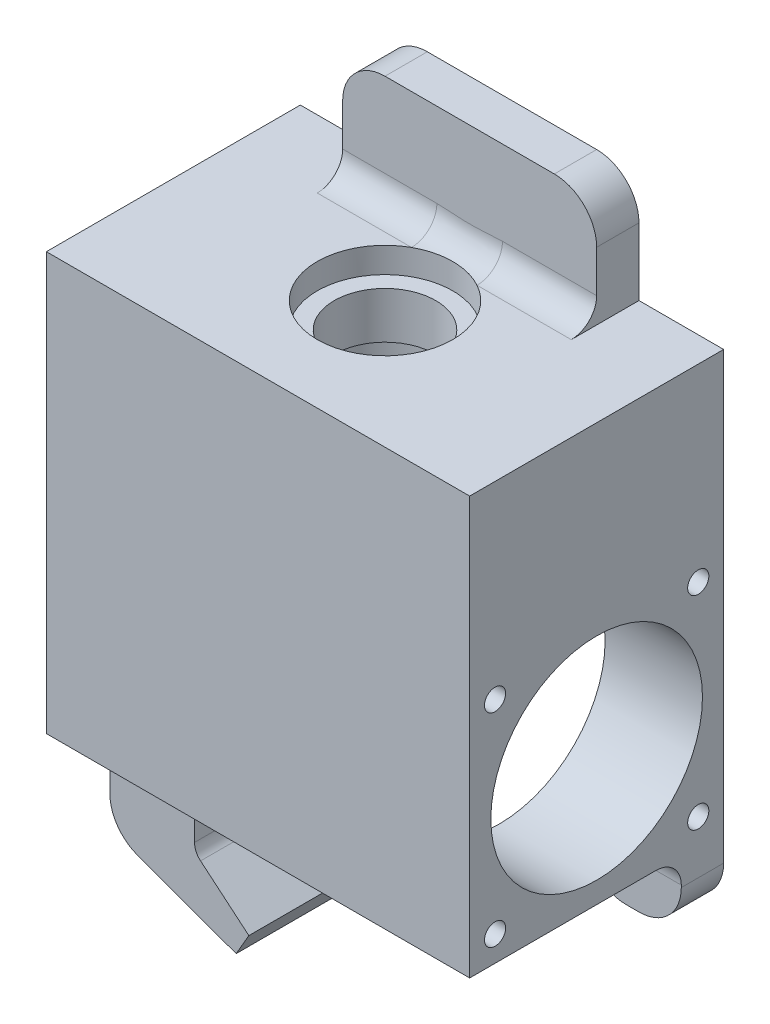
SolidWorks part; units mm, degrees
ref_plane "Спереди" through (0, 0, 0) normal (0, 0, 1) x (1, 0, 0)
ref_plane "Сверху" through (0, 0, 0) normal (0, 1, 0) x (1, 0, 0)
ref_plane "Справа" through (0, 0, 0) normal (1, 0, 0) x (0, 0, -1)
sketch "Эскиз1" plane through (0, 0, 0) normal (0, 0, 1) x (1, 0, 0)
  line L1 (25, -35.25) -> (-25, -35.25)
  line L2 (25, -35.25) -> (25, 35.25)
  line L3 (25, 35.25) -> (-25, 35.25)
  line L4 (-25, -35.25) -> (-25, 35.25)
  line L5 (25, -35.25) -> (-25, 35.25) construction
  line L6 (25, 35.25) -> (-25, -35.25) construction
  point P0 (0, 0)
  dimension "D1" = 50
  dimension "D2" = 70.5
extrude "Бобышка-Вытянуть1" add sketch "Эскиз1" along normal blind 30
sketch "Эскиз2" plane through (0, -35.25, 0) normal (0, -1, 0) x (1, 0, 0)
  line L0 (-25, 0) -> (25, 0) construction
  line L1 (-13.5, 15) -> (-13.5, 0)
  line L2 (-13.5, 0) -> (13.5, 0)
  line L3 (13.5, 0) -> (13.5, 15)
  arc A0 (13.5, 15) -> (-13.5, 15) centre (0, 15) ccw
  dimension "D1" = 27
  dimension "D2" = 15
extrude "Вырез-Вытянуть1" cut sketch "Эскиз2" against normal blind 46.05
ref_plane "Плоскость1" through (0, 0, 15) normal (0, 0, -1) x (-1, 0, 0)
sketch "Эскиз3" plane through (0, 0, 15) normal (0, 0, -1) x (-1, 0, 0)
  line L0 (0, 50.0613) -> (0, -61.5012) construction
  line L1 (0, 35.25) -> (0, 10.8)
  line L2 (0, 10.8) -> (-8, 10.8)
  line L3 (-8, 10.8) -> (-8, 13.8)
  line L4 (-8, 13.8) -> (-6, 13.8)
  line L5 (-6, 13.8) -> (-6, 19.3)
  line L6 (-6, 19.3) -> (-8, 19.3)
  line L7 (-8, 19.3) -> (-8, 35.25)
  line L8 (-8, 35.25) -> (0, 35.25)
  line L9 (-25, 35.25) -> (25, 35.25) construction
  line L10 (-13.5, -35.25) -> (-25, -35.25) construction
  line L11 (13.5, 10.8) -> (-13.5, 10.8) construction
  dimension "D1" = 16
  dimension "D2" = 12
  dimension "D3" = 49.05
  dimension "D4" = 5.5
revolve "Вырез-Повернуть1" cut sketch "Эскиз3" angle 360 about L0
sketch "Эскиз4" plane through (25, 0, 0) normal (1, 0, 0) x (0, 0, -1)
  line L0 (-5, -30) -> (-5, -35.25)
  line L2 (-8, -27) -> (-30, -27)
  line L3 (-30, -35.25) -> (-30, 35.25) construction
  line L4 (-30, -27) -> (-30, -35.25)
  line L5 (-30, -35.25) -> (0, -35.25) construction
  line L6 (-30, -35.25) -> (-5, -35.25)
  line L7 (0, -35.25) -> (0, 35.25) construction
  arc A0 (-5, -30) -> (-8, -27) centre (-8, -30) ccw
  dimension "D3" = 3
  dimension "D1" = 5
  dimension "D2" = 8.25
extrude "Вырез-Вытянуть2" cut sketch "Эскиз4" against normal blind 50
sketch "Эскиз5" plane through (25, 0, 0) normal (1, 0, 0) x (0, 0, -1)
  line L0 (0, -35.25) -> (0, 35.25) construction
  line L1 (-8, -27) -> (-30, -27) construction
  circle A0 centre (-15, -12) radius 12.5
  dimension "D3" = 25
  dimension "D1" = 15
  dimension "D2" = 15
extrude "Вырез-Вытянуть3" cut sketch "Эскиз5" against normal blind 50
sketch "Эскиз6" plane through (25, 0, 0) normal (1, 0, 0) x (0, 0, -1)
  line L1 (-27, -24) -> (-3, -24) construction
  line L2 (-27, -24) -> (-27, 0) construction
  line L3 (-27, 0) -> (-3, 0) construction
  line L4 (-3, -24) -> (-3, 0) construction
  line L5 (-27, -24) -> (-3, 0) construction
  line L6 (-27, 0) -> (-3, -24) construction
  circle A0 centre (-27, 0) radius 1.25
  circle A1 centre (-3, 0) radius 1.25
  circle A2 centre (-3, -24) radius 1.25
  circle A3 centre (-27, -24) radius 1.25
  point P0 (-15, -12)
  dimension "D2" = 2.5
  dimension "D1" = 24
extrude "Вырез-Вытянуть4" cut sketch "Эскиз6" against normal blind 6.5
fillet "Скругление1" radius 5 4 edges at (25, -35.25, 2.5) (13.5, -35.25, 2.5) (-13.5, -35.25, 2.5) (-25, -35.25, 2.5)
sketch "Эскиз7" plane through (0, 0, 15) normal (0, 0, -1) x (-1, 0, 0)
  line L0 (0, 28.3936) -> (0, -77.8751) construction
  line L1 (25, -27) -> (-25, -27) construction
  line L2 (48.4706, -21.9022) -> (-9.25, -55.2272) construction
  line L3 (38.8606, -47) -> (-57.2354, -47) construction
  line L4 (10.0801, -45.799) -> (8.5801, -43.201)
  line L5 (8.5801, -43.201) -> (14.2856, -38.4135)
  line L6 (15, -36.8814) -> (15, -27)
  line L7 (10.0801, -45.799) -> (21.7101, -41.5661)
  line L8 (25, -36.8676) -> (25, -27)
  line L9 (25, 35.25) -> (25, -27) construction
  line L10 (25, -27) -> (13.5, -27) construction
  line L11 (25, -27) -> (15, -27)
  arc A0 (14.2856, -38.4135) -> (15, -36.8814) centre (13, -36.8814) ccw
  arc A1 (21.7101, -41.5661) -> (25, -36.8676) centre (20, -36.8676) ccw
  point P1 (0, -47)
  point P8 (5, -47)
  point P14 (9.3301, -44.5)
  dimension "D8" = 5
  dimension "D9" = 2
  dimension "D1" = 20
  dimension "D2" = 30
  dimension "D3" = 5
  dimension "D4" = 3
  dimension "D5" = 5
  dimension "D6" = 10
  dimension "D7" = 10
  dimension "D10" = 10
extrude "Бобышка-Вытянуть2" add sketch "Эскиз7" along normal mid plane 15
sketch "Эскиз8" plane through (0, 0, 0) normal (0, 0, -1) x (-1, 0, 0)
  line L0 (-25, 35.25) -> (25, 35.25) construction
  line L1 (25, 35.25) -> (15, 35.25)
  line L2 (25, 35.25) -> (25, 22.3)
  line L3 (25, 22.3) -> (15, 22.3)
  line L4 (15, 35.25) -> (15, 22.3)
  line L6 (8, 19.3) -> (-8, 19.3) construction
  line L7 (25, 35.25) -> (25, -30.25) construction
  line L9 (-15, 22.3) -> (-25, 22.3)
  line L10 (-15, 22.3) -> (-15, 35.25)
  line L11 (-15, 35.25) -> (-25, 35.25)
  line L12 (-25, 22.3) -> (-25, 35.25)
  line L13 (15, 35.25) -> (-15, 35.25)
  line L14 (15, 35.25) -> (15, 22.3)
  line L15 (15, 22.3) -> (-15, 22.3)
  line L16 (-15, 35.25) -> (-15, 22.3)
  line M5 (-25, 35.25) -> (-25, -30.25)
  line M15 (25, -30.25) -> (25, 35.25)
  line M16 (25, 35.25) -> (-25, 35.25)
  dimension "D1" = 3
  dimension "D2" = 10
extrude "Вырез-Вытянуть5" cut sketch "Эскиз8" against normal blind 35 contours L4 L3 M16 M15 | L9 L10 M16 M5 region at (-20, 28.775, 0) region at (20, 28.775, 0)
extrude "Вырез-Вытянуть6" cut sketch "Эскиз8<3>" against normal blind 35 from offset 5 contours L15 L4 L10 M16 region at (0, 28.775, 0) offset against normal yes
sketch "Эскиз8<3>" plane through (0, 0, 0) normal (0, 0, -1) x (-1, 0, 0) same geometry as "Эскиз8"
fillet "Скругление2" radius 3 1 edges at (0, 22.3, 5)
fillet "Скругление3" radius 5 2 edges at (-15, 35.25, 2.5) (15, 35.25, 2.5)
equation "\"D1@Вырез-Вытянуть1\"=6.5+1.75+50.1-12.3"
equation "\"D3@Эскиз3\"=6.5+1.75+50.1-9.3"
